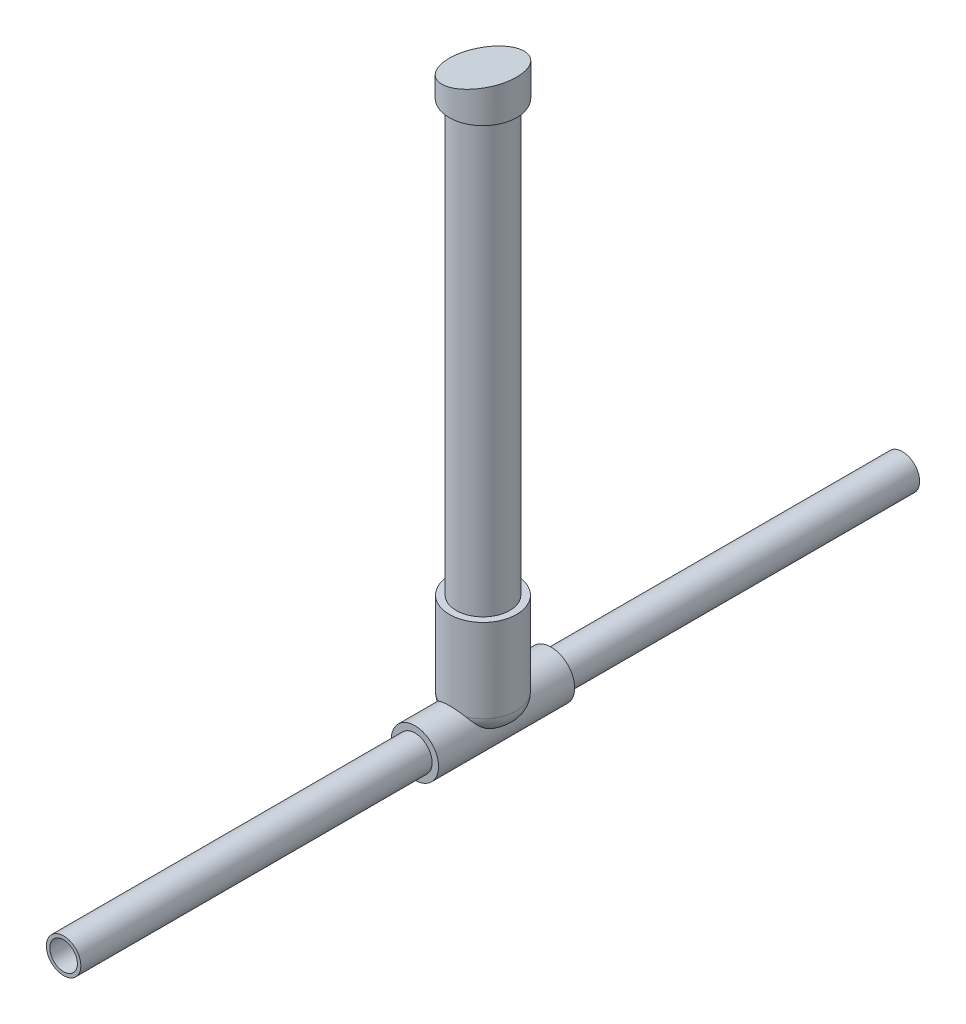
SolidWorks part; units mm, degrees
material "Hexcel AS4C (3000 Filaments)"
ref_plane "Front" through (0, 0, 0) normal (0, 0, 1) x (1, 0, 0)
ref_plane "Top" through (0, 0, 0) normal (0, 1, 0) x (1, 0, 0)
ref_plane "Right" through (0, 0, 0) normal (1, 0, 0) x (0, 0, -1)
sketch "Sketch1" plane through (0, 0, 0) normal (0, 0, 1) x (1, 0, 0)
  circle A0 centre (0, 0) radius 4.9848
  circle A1 centre (0, 0) radius 4.0005
  dimension "D1" = 9.9695
  dimension "D2" = 8.001
extrude "Boss-Extrude1" add sketch "Sketch1" along normal blind 242.57
ref_plane "Plane1" through (0, 0, 140.97) normal (0, 0, 1) x (1, 0, 0)
sketch "Sketch2" plane through (0, 0, 140.97) normal (0, 0, 1) x (1, 0, 0)
  circle A0 centre (0, 0) radius 6.8326
  circle A1 centre (0, 0) radius 4.9848
  dimension "D1" = 13.6652
extrude "Boss-Extrude2" add sketch "Sketch2" against normal blind 39.37
sketch "Sketch3" plane through (0, 0, 140.97) normal (0, 0, 1) x (1, 0, 0)
  line L0 (0, 6.8326) -> (0, -6.8326)
  circle A0 centre (0, 0) radius 6.8326 construction
ref_plane "Plane2" through (0, 6.8326, 0) normal (0, 1, 0) x (1, 0, 0)
sketch "Sketch4" plane through (0, 6.8326, 0) normal (0, 1, 0) x (1, 0, 0)
  line L0 (6.8326, -121.285) -> (-6.8326, -121.285)
  line L1 (6.8326, -140.97) -> (6.8326, -101.6) construction
  line L2 (-6.8326, -101.6) -> (-6.8326, -140.97) construction
  circle A0 centre (0, -121.285) radius 9.7155
  circle A1 centre (0, -121.285) radius 7.7851
  dimension "D1" = 19.431
  dimension "D2" = 15.5702
extrude "Boss-Extrude3" add sketch "Sketch4" along normal blind 22.86 and the other way blind 6.35
sketch "Sketch5" plane through (0, 29.6926, 0) normal (0, 1, 0) x (1, 0, 0)
  circle A0 centre (0, -121.285) radius 7.747
  circle A1 centre (0, -121.285) radius 9.7155
  dimension "D1" = 15.494
extrude "Cut-Extrude1" cut sketch "Sketch5" against normal blind 22.86 contours A0
fillet "Fillet1" radius 5.08 6 edges at (6.8155, 0.4826, 121.285) (0.3383, -6.8242, 130.9946) (-1.5635, -6.6513, 111.6961) (-6.8155, 0.4826, 121.285) (9.7155, 0.4826, 121.285) (-9.7155, 0.4826, 121.285)
sketch "Sketch6" plane through (0, 29.6926, 0) normal (0, 1, 0) x (1, 0, 0)
  circle A0 centre (0, -121.285) radius 7.747
  circle A1 centre (0, -121.285) radius 6.9215
  dimension "D1" = 13.843
extrude "Boss-Extrude5" add sketch "Sketch6" along normal blind 124.46 and the other way blind 15.24
sketch "Sketch7" plane through (0, 154.1526, 0) normal (0, 1, 0) x (1, 0, 0)
  circle A0 centre (0, -121.285) radius 9.779
  dimension "D1" = 19.558
extrude "Boss-Extrude6" add sketch "Sketch7" along normal blind 10.16
sketch "Sketch8" plane through (0, 0, 101.6) normal (0, 0, -1) x (-1, 0, 0)
  line L1 (-9.779, 164.3126) -> (-9.779, 154.1526) construction
  line L3 (9.779, 164.3126) -> (-9.779, 164.3126) construction
  line L4 (9.779, 164.3126) -> (-9.779, 164.3126)
  line L5 (9.779, 164.3126) -> (9.779, 159.2326)
  line L6 (9.779, 154.1526) -> (9.779, 164.3126) construction
  line L7 (9.779, 159.2326) -> (-9.779, 164.3126)
extrude "Cut-Extrude2" cut sketch "Sketch8" against normal through all
